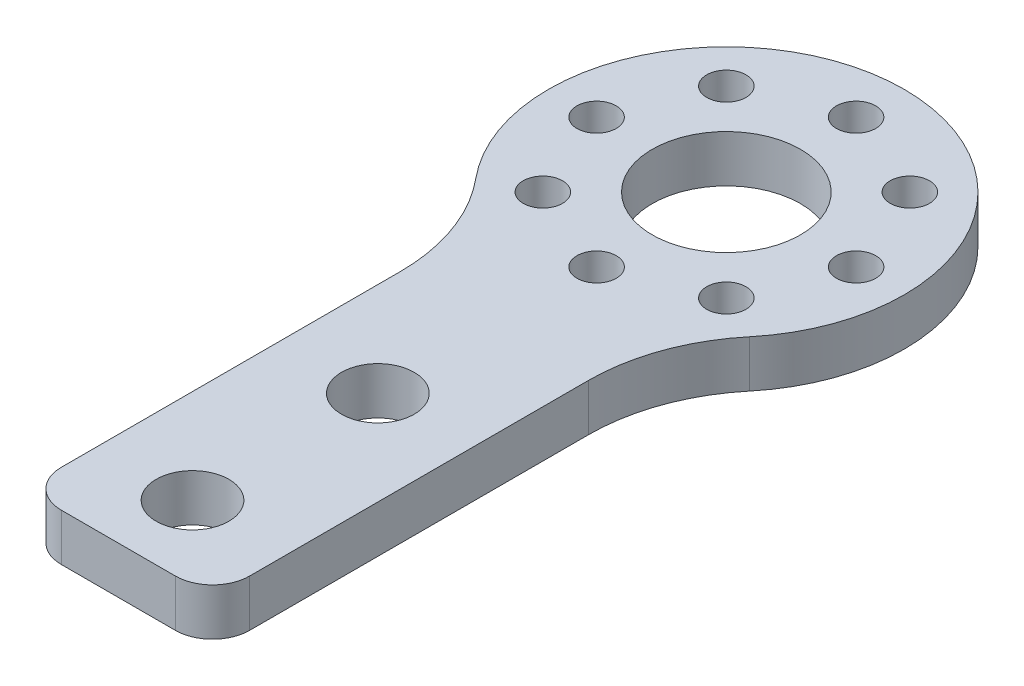
SolidWorks part; units mm, degrees
material "1060 Alloy"
ref_plane "Front Plane" through (0, 0, 0) normal (0, 0, 1) x (1, 0, 0)
ref_plane "Top Plane" through (0, 0, 0) normal (0, 1, 0) x (1, 0, 0)
ref_plane "Right Plane" through (0, 0, 0) normal (1, 0, 0) x (0, 0, -1)
sketch "Sketch1" plane through (0, 0, 0) normal (0, 1, 0) x (1, 0, 0)
  line L0 (-12.7, -82) -> (12.7, -82)
  line L1 (12.7, -82) -> (12.7, -20.3644)
  line L2 (-12.7, -82) -> (-12.7, -20.3644)
  line L3 (0, -82) -> (0, -47) construction
  arc A0 (12.7, -20.3644) -> (-12.7, -20.3644) centre (0, 0) ccw
  point P5 (0, -82)
  point P9 (0, -72)
  point P11 (0, -47)
  dimension "D2" = 48
  dimension "D1" = 25.4
  dimension "D3" = 47
  dimension "D4" = 25
  dimension "D5" = 10
extrude "Boss-Extrude1" add sketch "Sketch1" along normal blind 6.35 contours A0 L2 L0 L1
sketch "Sketch2" plane through (0, 0, 0) normal (0, -1, 0) x (1, 0, 0)
  circle A0 centre (0, 0) radius 17.5 construction
  point P3 (17.5, 0)
  point P4 (0, 0)
  point P5 (0, 0)
  point P6 (12.3744, -12.3744)
  point P7 (0, -17.5)
  point P8 (-12.3744, -12.3744)
  point P9 (-17.5, 0)
  point P10 (-12.3744, 12.3744)
  point P11 (0, 17.5)
  point P12 (12.3744, 12.3744)
  point P13 (0, 0)
  point P14 (0, -17.5)
  dimension "D2" = 35
  dimension "D1" = 8
hole_wizard "M5 Clearance Hole1" positions "Sketch3" profile "Sketch4" hole size "M5" standard "ANSI Metric" end condition through all
sketch "Sketch3" plane through (0, 0, 0) normal (0, -1, 0) x (-1, 0, 0)
  point P0 (0, 17.5)
  point P3 (12.3744, 12.3744)
  point P6 (17.5, 0)
  point P9 (12.3744, -12.3744)
  point P12 (0, -17.5)
  point P15 (-12.3744, -12.3744)
  point P18 (-17.5, 0)
  point P21 (-12.3744, 12.3744)
sketch "Sketch4" plane through (0, 0, -17.5) normal (1, 0, 0) x (0, 0, -1)
  line L0 (0, 0) -> (0, 6.35)
  line L1 (0, 6.35) -> (2.65, 6.35)
  line L2 (2.65, 6.35) -> (2.65, 0)
  line L5 (2.65, 0) -> (0, 0)
  line L11 (0, -6.35) -> (0, 107.95) construction
  dimension "Thru Hole Dia." = 5.3
  dimension "Thru Hole Depth" = 6.35
sketch "Sketch5" plane through (0, 0, 0) normal (0, -1, 0) x (1, 0, 0)
  circle A0 centre (0, 0) radius 10
  dimension "D1" = 20
extrude "Cut-Extrude1" cut sketch "Sketch5" against normal through all
fillet "Fillet1" radius 25 2 edges at (-12.7, 3.175, 20.3644) (12.7, 3.175, 20.3644)
fillet "Fillet2" radius 5 2 edges at (12.7, 3.175, 82) (-12.7, 3.175, 82)
hole_wizard "3/8 Clearance Hole1" positions "Sketch9" profile "Sketch10" hole size "3/8" standard "ANSI Inch" end condition through all
sketch "Sketch9" plane through (0, 0, 0) normal (0, -1, 0) x (-1, 0, 0)
  point P0 (0, -47)
  point P3 (0, -72)
sketch "Sketch10" plane through (0, 0, 47) normal (1, 0, 0) x (0, 0, -1)
  line L0 (0, 0) -> (0, 6.35)
  line L1 (0, 6.35) -> (4.9022, 6.35)
  line L2 (4.9022, 6.35) -> (4.9022, 0)
  line L5 (4.9022, 0) -> (0, 0)
  line L11 (0, -6.35) -> (0, 107.95) construction
  dimension "Thru Hole Dia." = 9.8044
  dimension "Thru Hole Depth" = 6.35
